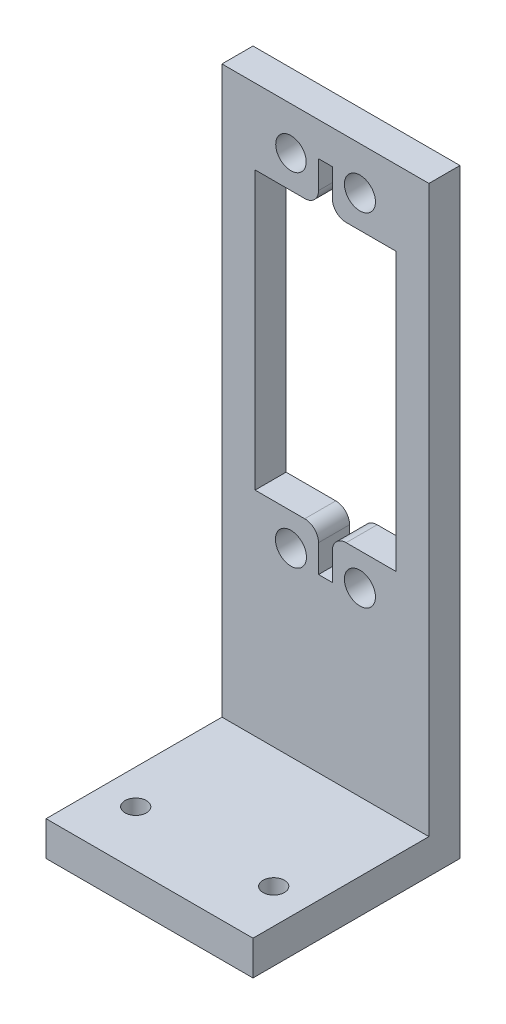
SolidWorks part; units mm, degrees
ref_plane "前视基准面" through (0, 0, 0) normal (0, 0, 1) x (1, 0, 0)
ref_plane "上视基准面" through (0, 0, 0) normal (0, 1, 0) x (1, 0, 0)
ref_plane "右视基准面" through (0, 0, 0) normal (1, 0, 0) x (0, 0, -1)
sketch "草图1" plane through (0, 0, 0) normal (0, 0, 1) x (1, 0, 0)
  line L1 (10.2, -20.1) -> (-10.2, -20.1)
  line L2 (10.2, -20.1) -> (10.2, 20.1)
  line L3 (10.2, 20.1) -> (-10.2, 20.1)
  line L4 (-10.2, -20.1) -> (-10.2, 20.1)
  line L5 (10.2, -20.1) -> (-10.2, 20.1) construction
  line L6 (10.2, 20.1) -> (-10.2, -20.1) construction
  line L7 (15, -31) -> (-15, -31)
  line L8 (15, -31) -> (15, 31)
  line L9 (15, 31) -> (-15, 31)
  line L10 (-15, -31) -> (-15, 31)
  line L11 (15, -31) -> (-15, 31) construction
  line L12 (15, 31) -> (-15, -31) construction
  point P0 (0, 0)
  point P5 (0, 0)
  dimension "D1" = 20.4
  dimension "D2" = 40.2
  dimension "D3" = 30
  dimension "D4" = 62
extrude "凸台-拉伸1" add sketch "草图1" along normal blind 4.5
sketch "草图3" plane through (0, 0, 0) normal (0, 0, -1) x (-1, 0, 0)
  circle A0 centre (-5, -24.8) radius 2.25
  circle A1 centre (5, -24.8) radius 2.25
  circle A2 centre (-5, 24.8) radius 2.25
  circle A3 centre (5, 24.8) radius 2.2065
extrude "切除-拉伸1" cut sketch "草图3" against normal through all
sketch "草图4" plane through (0, 31, 0) normal (0, 1, 0) x (1, 0, 0)
  line L4 (15, 0) -> (-15, 0)
  line L5 (-15, 0) -> (-15, -4.5)
  line L6 (-15, -4.5) -> (15, -4.5)
  line L7 (15, -4.5) -> (15, 0)
  line L8 (15, 0) -> (-15, 0)
  line L9 (-15, 0) -> (-15, -4.5)
  line L10 (-15, -4.5) -> (15, -4.5)
  line L11 (15, -4.5) -> (15, 0)
  dimension "D1" = 0
sketch "草图5" plane through (0, -31, 0) normal (0, -1, 0) x (1, 0, 0)
  line L4 (-15, 0) -> (15, 0)
  line L5 (15, 0) -> (15, 4.5)
  line L6 (15, 4.5) -> (-15, 4.5)
  line L7 (-15, 4.5) -> (-15, 0)
  line L8 (-15, 0) -> (15, 0)
  line L9 (15, 0) -> (15, 4.5)
  line L10 (15, 4.5) -> (-15, 4.5)
  line L11 (-15, 4.5) -> (-15, 0)
  dimension "D1" = 0
extrude "凸台-拉伸3" add sketch "草图5" along normal blind 20
sketch "草图6" plane through (0, -51, 0) normal (0, -1, 0) x (1, 0, 0)
  line L0 (-15, 4.5) -> (-15, 0) construction
  line L1 (15, 0) -> (-15, 0)
  line L2 (15, 0) -> (15, 30)
  line L3 (15, 30) -> (-15, 30)
  line L4 (-15, 0) -> (-15, 30)
  dimension "D1" = 30
extrude "凸台-拉伸4" add sketch "草图6" along normal blind 5
sketch "草图7" plane through (0, -56, 0) normal (0, -1, 0) x (1, 0, 0)
  line L0 (0, 30) -> (0, 22) construction
  line L1 (15, 30) -> (-15, 30) construction
  line L2 (0, 22) -> (10, 22) construction
  circle A0 centre (10, 22) radius 1.55
  circle A1 centre (-10, 22) radius 1.55
  dimension "D1" = 8
  dimension "D3" = 3.1
  dimension "D2" = 10
extrude "切除-拉伸2" cut sketch "草图7" against normal through all
sketch "草图8" plane through (0, 0, 4.5) normal (0, 0, 1) x (1, 0, 0)
  line L0 (0, -20.1) -> (0, -26.5553) construction
  line L1 (-10.2, -20.1) -> (10.2, -20.1) construction
  line L2 (0, 0) -> (13.0244, 0) construction
  line L3 (1, 20.1) -> (-1, 26.1) construction
  line L4 (1, -26.1) -> (-1, -26.1)
  line L5 (1, -26.1) -> (1, -20.1)
  line L6 (1, -20.1) -> (-1, -20.1)
  line L7 (-1, -26.1) -> (-1, -20.1)
  line L8 (1, -26.1) -> (-1, -20.1) construction
  line L9 (1, -20.1) -> (-1, -26.1) construction
  line L10 (1, 26.1) -> (-1, 20.1) construction
  line L11 (0, 20.1) -> (0, 26.5553) construction
  line L12 (-1, 26.1) -> (-1, 20.1)
  line L13 (1, 20.1) -> (-1, 20.1)
  line L14 (1, 26.1) -> (1, 20.1)
  line L15 (1, 26.1) -> (-1, 26.1)
  point P7 (0, -23.1)
  point P18 (0, 23.1)
  dimension "D1" = 2
  dimension "D2" = 6
extrude "切除-拉伸3" cut sketch "草图8" against normal through all
fillet "圆角1" radius 2 4 edges at (1, 20.1, 2.25) (-1, 20.1, 2.25) (1, -20.1, 2.25) (-1, -20.1, 2.25)
